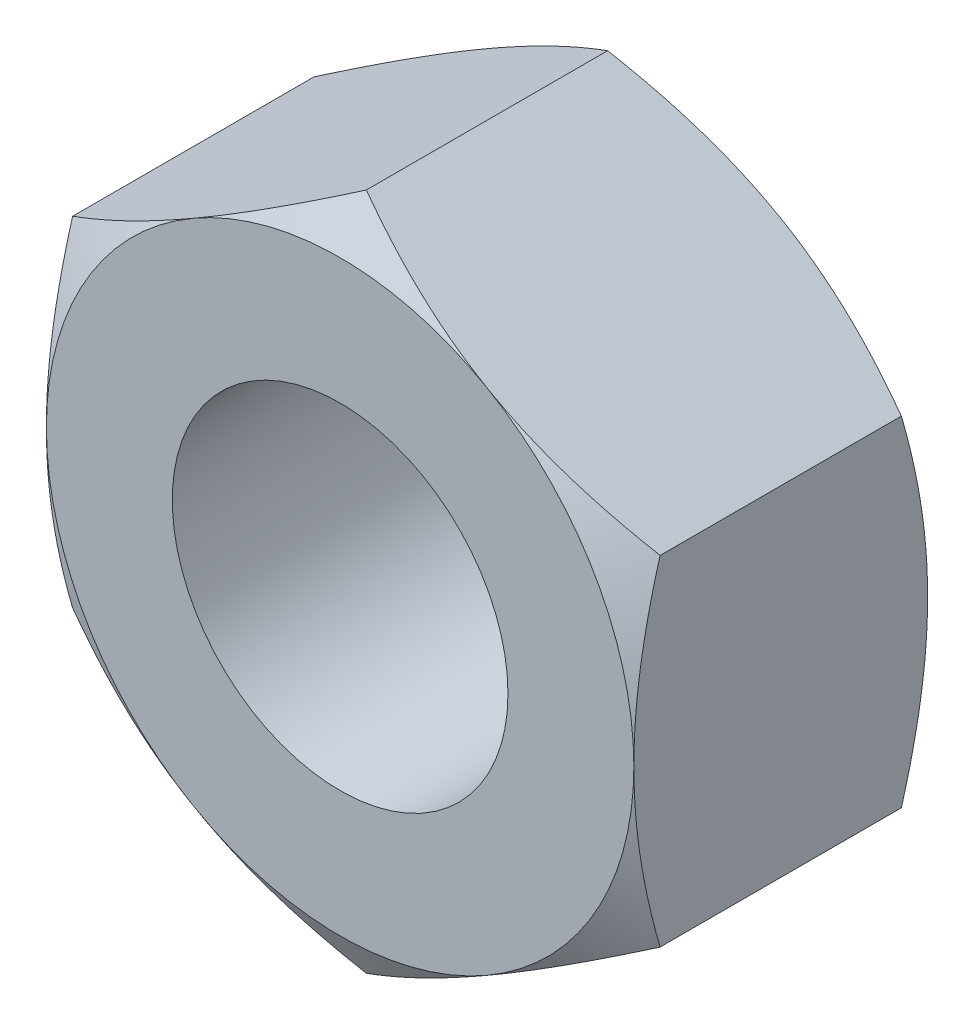
SolidWorks part; units mm, degrees
ref_plane "Front" through (0, 0, 0) normal (0, 0, 1) x (1, 0, 0)
ref_plane "Top" through (0, 0, 0) normal (0, 1, 0) x (1, 0, 0)
ref_plane "Right" through (0, 0, 0) normal (1, 0, 0) x (0, 0, -1)
sketch "Sketch1" plane through (0, 0, 0) normal (0, 0, 1) x (1, 0, 0)
  line L1 (-5.5562, 3.2079) -> (-5.5562, -3.2079)
  line L2 (-5.5562, -3.2079) -> (0, -6.4158)
  line L3 (0, -6.4158) -> (5.5562, -3.2079)
  line L4 (5.5562, -3.2079) -> (5.5562, 3.2079)
  line L5 (5.5562, 3.2079) -> (0, 6.4158)
  line L6 (0, 6.4158) -> (-5.5562, 3.2079)
  circle A0 centre (0, 0) radius 5.5562 construction
  circle A1 centre (0, 0) radius 3.175
  point P10 (0, 3.175)
  dimension "hex" = 11.1125
  dimension "dia" = 6.35
extrude "Extrude1" add sketch "Sketch1" along normal mid plane 5.5562
sketch "Sketch4" plane through (0, 0, -2.7781) normal (0, 0, -1) x (-1, 0, 0)
  circle A0 centre (0, 0) radius 3.175 construction
  circle A1 centre (0, 0) radius 3.175
curve "Helix/Spiral3" [suppressed] pitch 1.27 height 6.6675 turns 5.25
sketch "Sketch3" plane through (0, 0, 0) normal (1, 0, 0) x (0, 0, -1)
  line L0 (2.7781, 3.175) -> (3.8894, 3.175)
  line L1 (3.8894, 3.175) -> (3.4131, 2.3501)
  line L2 (3.4131, 2.3501) -> (3.2544, 2.3501)
  line L3 (3.2544, 2.3501) -> (2.7781, 3.175)
  line L4 (3.0163, 2.7626) -> (3.6513, 2.7626) construction
  dimension "D1" = 60
  dimension "D2" = 0.635
  dimension "D3" = 0.1588
sweep "Sweep1" [suppressed] add profiles "Sketch3" path "Helix/Spiral3"
sketch "Sketch6" [suppressed] plane through (0, 0, 0) normal (1, 0, 0) x (0, 0, -1)
  line L0 (-3.0956, 3.4925) -> (-2.4606, 2.8575)
  line L1 (-2.4606, 2.8575) -> (-2.4606, 0) construction
  line L2 (3.9291, 0) -> (-3.9291, 0) construction
  line L3 (-2.4606, 0) -> (-3.8894, 0)
  line L4 (-3.8894, 0) -> (-3.8894, 3.4925)
  line L5 (-3.8894, 3.4925) -> (-3.0956, 3.4925)
  line L6 (-2.4606, 2.8575) -> (0.3969, 0)
  line L7 (0.3969, 0) -> (-2.4606, 0)
  line L8 (-2.7781, -3.2079) -> (-2.7781, 3.2079) construction
  point P2 (-2.7781, 3.175)
  dimension "D2" = 0.635
  dimension "D1" = 45
revolve "Cut-Revolve1" [suppressed] cut sketch "Sketch6" angle 360 about L3
sketch "Sketch7" plane through (0, 0, 2.7781) normal (0, 0, 1) x (1, 0, 0)
  circle A0 centre (0, 0) radius 5.5562 construction
  circle A1 centre (0, 0) radius 5.5562
extrude "Extrude2" cut sketch "Sketch7" against normal blind 25.4 draft 60 flip side to cut
mirror "Mirror1" about plane through (0, 0, 0) normal (0, 0, 1) of "Extrude2", "Cut-Revolve1"
sketch "Sketch8" [suppressed] plane through (0, 0, 2.7781) normal (0, 0, 1) x (1, 0, 0)
  line L0 (-2.2451, 2.2451) -> (0, 0) construction
  line L1 (0, -3.9291) -> (0, 3.9291) construction
  circle A0 centre (0, 0) radius 3.175 construction
  point P0 (-2.2451, 2.2451)
  dimension "D1" = 45
equation "\"D3@Helix/Spiral3\" = \"length@Extrude1\" * 1.2"
equation "\"D2@Sketch3\" = \"D4@Helix/Spiral3\" * .5"
equation "\"D3@Sketch3\" = \"D4@Helix/Spiral3\" * .125"
equation "\"D2@Sketch6\" = \"D4@Helix/Spiral3\" * .5"
